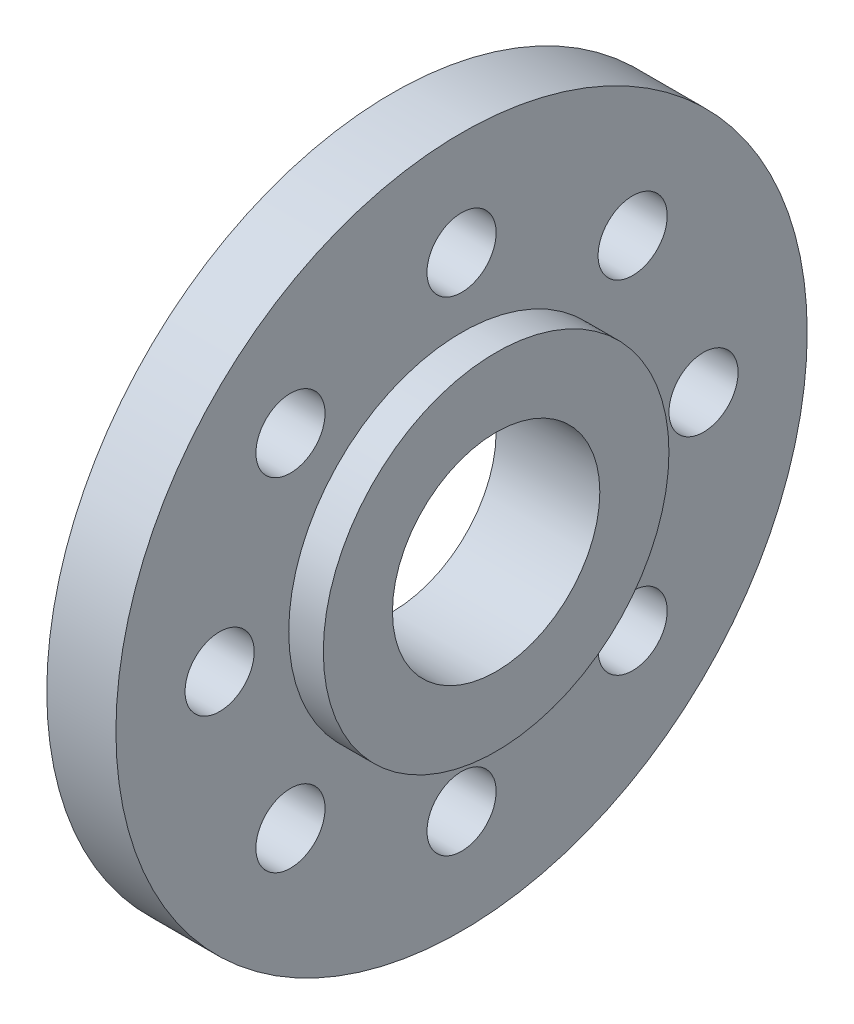
SolidWorks part; units mm, degrees
ref_plane "前视基准面" through (0, 0, 0) normal (0, 0, 1) x (1, 0, 0)
ref_plane "上视基准面" through (0, 0, 0) normal (0, 1, 0) x (1, 0, 0)
ref_plane "右视基准面" through (0, 0, 0) normal (1, 0, 0) x (0, 0, -1)
sketch "草图1" plane through (0, 0, 0) normal (1, 0, 0) x (0, 0, -1)
  circle A0 centre (0, 0) radius 10
  dimension "D1" = 20
extrude "凸台-拉伸1" add sketch "草图1" along normal blind 2
sketch "草图3" plane through (2, 0, 0) normal (1, 0, 0) x (0, 0, -1)
  circle A0 centre (0, 0) radius 3
  dimension "D1" = 6
extrude "切除-拉伸1" cut sketch "草图3" against normal through all
sketch "草图4" plane through (2, 0, 0) normal (1, 0, 0) x (0, 0, -1)
  circle A0 centre (0, 0) radius 5
  circle A1 centre (0, 0) radius 3
  dimension "D1" = 10
extrude "凸台-拉伸2" add sketch "草图4" along normal blind 1
sketch "草图5" plane through (0, 0, 0) normal (-1, 0, 0) x (0, 0, 1)
  circle A0 centre (0, 7) radius 1
  dimension "D1" = 2
  dimension "D2" = 7
extrude "切除-拉伸2" cut sketch "草图5" against normal through all
ref_axis "基准轴1" through (0, 0, 0) along (1, 0, 0)
pattern_circular "阵列(圆周)1" count 8 over 360 about axis through (0, 0, 0) along (1, 0, 0) of "切除-拉伸2"
